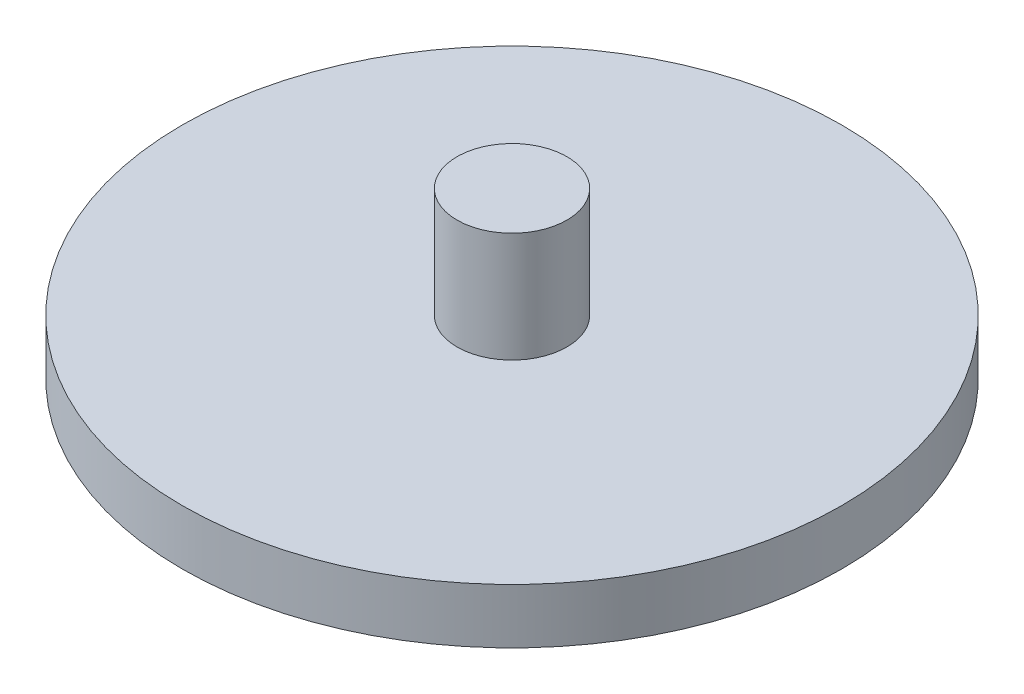
SolidWorks part; units mm, degrees
ref_plane "Front Plane" through (0, 0, 0) normal (0, 0, 1) x (1, 0, 0)
ref_plane "Top Plane" through (0, 0, 0) normal (0, 1, 0) x (1, 0, 0)
ref_plane "Right Plane" through (0, 0, 0) normal (1, 0, 0) x (0, 0, -1)
sketch "Sketch1" plane through (0, 0, 0) normal (0, 1, 0) x (1, 0, 0)
  circle A0 centre (0, 0) radius 25.4
  dimension "D1" = 50.8
extrude "Boss-Extrude1" add sketch "Sketch1" along normal blind 50.8
sketch "Sketch2" plane through (0, 0, 0) normal (0, -1, 0) x (1, 0, 0)
  circle A0 centre (0, 0) radius 152.4
  dimension "D1" = 304.8
extrude "Boss-Extrude2" add sketch "Sketch2" along normal blind 25.4
sketch "Sketch3" plane through (0, -25.4, 0) normal (0, -1, 0) x (1, 0, 0)
  line L0 (-63.5, 0) -> (63.5, 0)
  line L1 (27.94, 0) -> (-27.94, 0) construction
  line L2 (0, -27.94) -> (0, 27.94) construction
  line L3 (-63.5, -27.94) -> (-63.5, 27.94)
  line L4 (-63.5, 27.94) -> (63.5, 27.94)
  line L5 (63.5, 27.94) -> (63.5, -3.2168)
  line L6 (63.5, -27.94) -> (63.5, 3.2168)
  line L7 (-63.5, -27.94) -> (63.5, -27.94)
  point P8 (0, 0)
  dimension "D1" = 55.88
  dimension "D2" = 127
extrude "Boss-Extrude3" add sketch "Sketch3" along normal blind 55.88 contours L5 L4 L3 L0 | L3 L7 L6 L5 L0 region at (0, -25.4, 13.97) region at (0, -25.4, -13.97)
sketch "Sketch4" plane through (-63.5, 0, 0) normal (-1, 0, 0) x (0, 0, 1)
  line L0 (-27.94, -25.4) -> (27.94, -81.28)
  circle A0 centre (0, -53.34) radius 20.32
extrude "Cut-Extrude1" cut sketch "Sketch4" against normal through all contours A0
